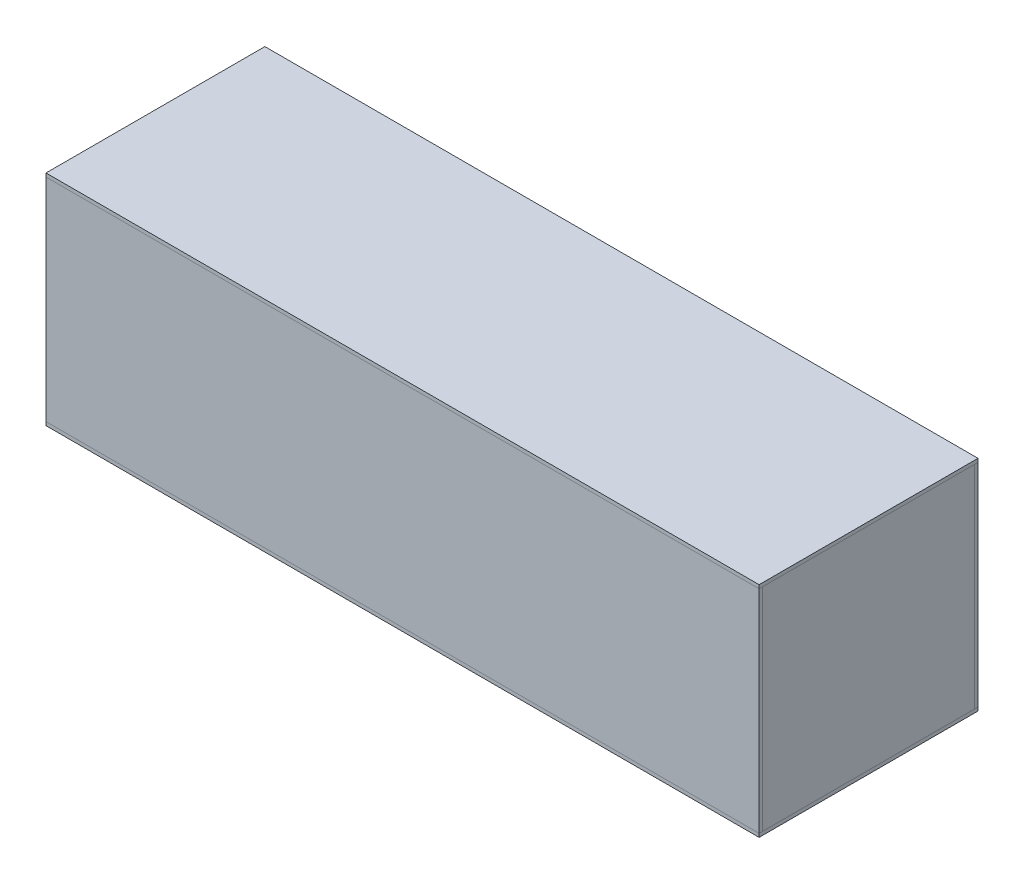
SolidWorks part; units mm, degrees
material "Acrylic (Medium-high impact)"
ref_plane "Front Plane" through (0, 0, 0) normal (0, 0, 1) x (1, 0, 0)
ref_plane "Top Plane" through (0, 0, 0) normal (0, 1, 0) x (1, 0, 0)
ref_plane "Right Plane" through (0, 0, 0) normal (1, 0, 0) x (0, 0, -1)
sketch "SKELETON" plane through (0, 0, 0) normal (0, 1, 0) x (1, 0, 0)
  line L0 (-500, -150) -> (500, 150) construction
  line L1 (-500, -150) -> (500, -150)
  line L2 (-500, -150) -> (-500, 150)
  line L3 (-500, 150) -> (500, 150)
  line L4 (500, -150) -> (500, 150)
  line L5 (-500, 150) -> (500, -150) construction
  line L6 (-505, 155) -> (505, 155)
  line L7 (505, -155) -> (505, 155)
  line L8 (-505, -155) -> (505, -155)
  line L9 (-505, -155) -> (-505, 155)
  line L10 (-500, 150) -> (-505, 150)
  line L11 (500, 150) -> (505, 150)
  line L12 (500, -150) -> (505, -150)
  line L13 (-500, -150) -> (-505, -150)
  point P4 (0, 0)
  dimension "D1" = 1000
  dimension "D2" = 300
  dimension "D3" = 5
extrude "Bottom" add sketch "SKELETON" against normal blind 5 contours L1 L4 L3 L2 | L3 L11 L7 L6 L9 L10 | L13 L2 L10 L9 | L1 L13 L9 L8 L7 L12 | L4 L12 L7 L11 region at (0, 0, 0) region at (-502.5, 0, 0) region at (0, 0, 152.5) region at (502.5, 0, 0) region at (0, 0, -152.5)
extrude "long-side" add sketch "SKELETON<3>" along normal blind 300 separate body contours L3 L11 L7 L6 L9 L10 | L1 L13 L9 L8 L7 L12 region at (0, 0, 152.5) region at (0, 0, -152.5)
sketch "SKELETON<3>" plane through (0, 0, 0) normal (0, 1, 0) x (1, 0, 0) same geometry as "SKELETON"
extrude "Short-side" add sketch "SKELETON<4>" along normal blind 300 separate body contours L4 L12 L7 L11 | L13 L2 L10 L9 region at (-502.5, 0, 0) region at (502.5, 0, 0)
sketch "SKELETON<4>" plane through (0, 0, 0) normal (0, 1, 0) x (1, 0, 0) same geometry as "SKELETON"
extrude "Top" add sketch "SKELETON<5>" along normal blind 5 from surface separate body contours L1 L4 L3 L2 | L1 L13 L9 L8 L7 L12 | L3 L11 L7 L6 L9 L10 | L13 L2 L10 L9 | L4 L12 L7 L11 region at (0, 0, 0) region at (-502.5, 0, 0) region at (0, 0, 152.5) region at (502.5, 0, 0) region at (0, 0, -152.5) starting at face at (0, 300, -152.5)
sketch "SKELETON<5>" plane through (0, 0, 0) normal (0, 1, 0) x (1, 0, 0) same geometry as "SKELETON"
